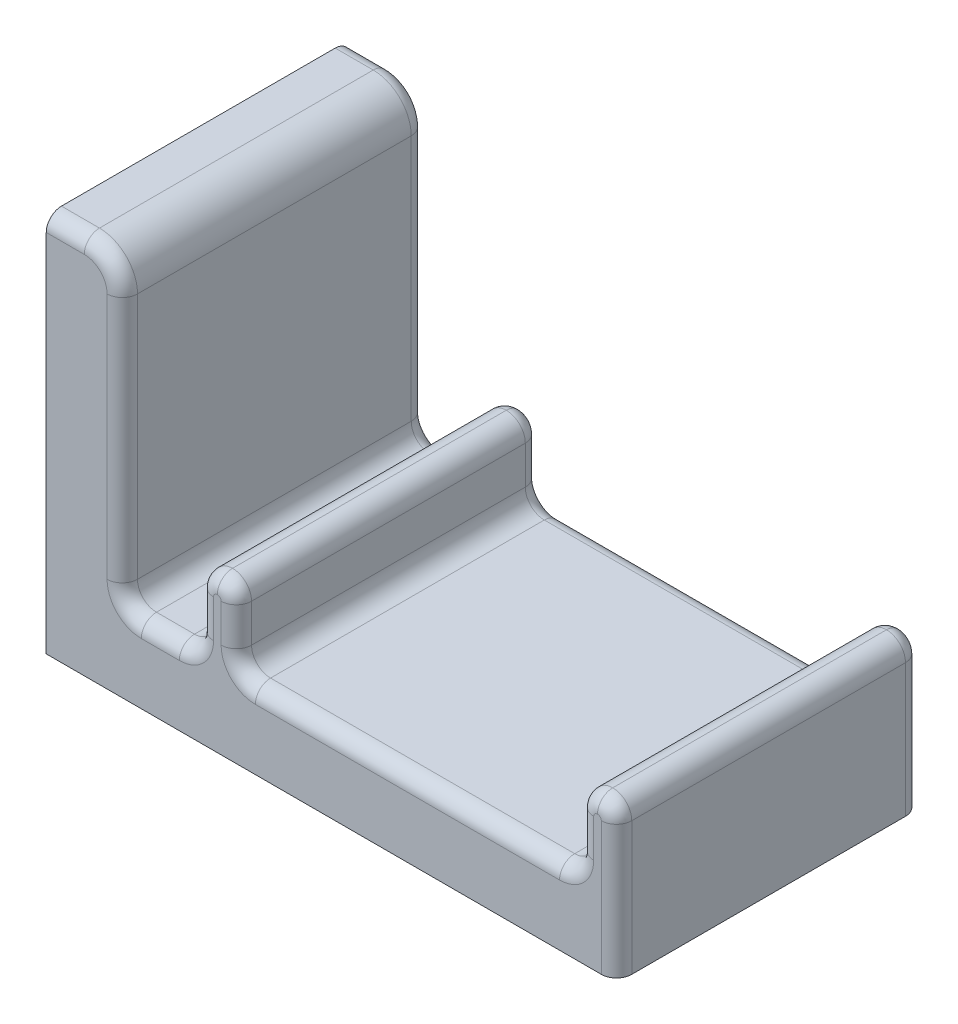
SolidWorks part; units mm, degrees
ref_plane "前基準面" through (0, 0, 0) normal (0, 0, 1) x (1, 0, 0)
ref_plane "上基準面" through (0, 0, 0) normal (0, 1, 0) x (1, 0, 0)
ref_plane "右基準面" through (0, 0, 0) normal (1, 0, 0) x (0, 0, -1)
sketch "草圖1" plane through (0, 0, 0) normal (0, 0, 1) x (1, 0, 0)
  line L0 (-39.7324, -6.4063) -> (-29.7324, -6.4063)
  line L1 (-39.7324, 33.5938) -> (-29.7324, 33.5938)
  line L2 (-39.7324, 33.5938) -> (-39.7324, -6.4063)
  line L4 (-29.7324, 33.5938) -> (-29.7324, -6.4063)
  line L14 (-39.7324, -6.4063) -> (35.2676, -6.4063)
  line L15 (-39.7324, -6.4063) -> (-39.7324, -16.4063)
  line L16 (-39.7324, -16.4063) -> (35.2676, -16.4063)
  line L17 (35.2676, -6.4063) -> (35.2676, -16.4063)
  line L18 (30.2676, -6.4063) -> (35.2676, -6.4063)
  line L19 (30.2676, -6.4063) -> (30.2676, 3.5937)
  line L20 (30.2676, 3.5937) -> (35.2676, 3.5937)
  line L21 (35.2676, -6.4063) -> (35.2676, 3.5937)
  line L22 (-14.7324, -6.4063) -> (-19.7324, -6.4063)
  line L23 (-14.7324, -6.4063) -> (-14.7324, 3.5937)
  line L24 (-14.7324, 3.5937) -> (-19.7324, 3.5937)
  line L25 (-19.7324, -6.4063) -> (-19.7324, 3.5937)
  dimension "D1" = 10
  dimension "D2" = 40
  dimension "D3" = 10
  dimension "D4" = 75
  dimension "D5" = 5
  dimension "D6" = 10
  dimension "D7" = 10
  dimension "D8" = 5
  dimension "D9" = 30
extrude "填料-伸長1" add sketch "草圖1" along normal blind 40 contours L4 L1 L2 L0 | L17 L14 L0 L15 L16 | L25 L24 L23 L22 | L21 L20 L19 L18 region at (-34.7324, 13.5938, 0) region at (-2.2324, -11.4063, 0)
fillet "圓角2" radius 5 1 edges at (-29.7324, 33.5938, 20)
fillet "圓角3" radius 2.5 2 edges at (-19.7324, -6.4063, 20) (-29.7324, -6.4063, 20)
fillet "圓角4" radius 2.5 6 edges at (30.2676, -6.4063, 20) (30.2676, 3.5937, 20) (35.2676, 3.5937, 20) (-14.7324, -6.4063, 20) (-14.7324, 3.5937, 20) (-19.7324, 3.5937, 20)
fillet "圓角6" radius 2 34 edges at (-37.2324, 33.5938, 40) (-31.1969, 32.1293, 40) (-29.7324, 12.3437, 40) (-29.0002, -5.674, 40) (-24.7324, -6.4063, 40) (-20.4646, -5.674, 40) (-19.7324, -1.4063, 40) (-19.0002, 2.8615, 40) (-15.4646, 2.8615, 40) (-14.7324, -1.4063, 40) (-14.0002, -5.674, 40) (35.2676, -7.6563, 40) (34.5354, 2.8615, 40) (30.9998, 2.8615, 40) (30.2676, -1.4063, 40) (29.5354, -5.674, 40) (-37.2324, 33.5938, 0) (-31.1969, 32.1293, 0) (-29.7324, 12.3437, 0) (-29.0002, -5.674, 0) (-24.7324, -6.4063, 0) (-20.4646, -5.674, 0) (-19.7324, -1.4063, 0) (-19.0002, 2.8615, 0) (-15.4646, 2.8615, 0) (-14.7324, -1.4063, 0) (-14.0002, -5.674, 0) (35.2676, -7.6563, 0) (34.5354, 2.8615, 0) (30.9998, 2.8615, 0) (30.2676, -1.4063, 0) (29.5354, -5.674, 0) (7.7676, -6.4063, 40) (7.7676, -6.4063, 0)
